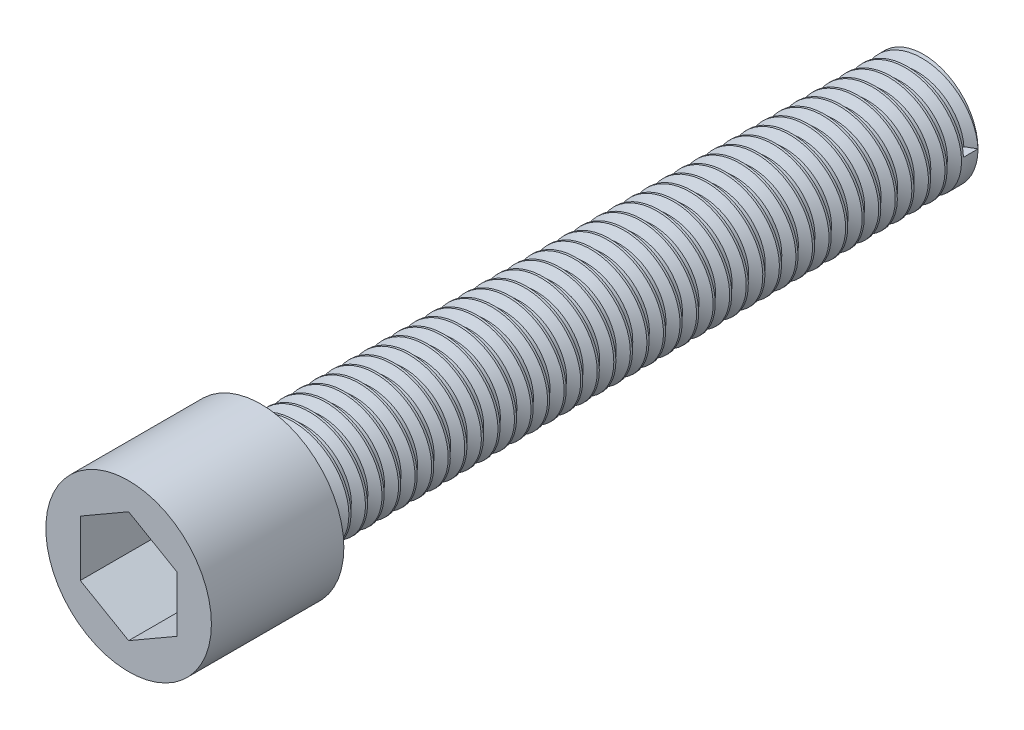
SolidWorks part; units mm, degrees
material "Aço carbono simples"
ref_plane "Plano frontal" through (0, 0, 0) normal (0, 0, 1) x (1, 0, 0)
ref_plane "Plano superior" through (0, 0, 0) normal (0, 1, 0) x (1, 0, 0)
ref_plane "Plano direito" through (0, 0, 0) normal (1, 0, 0) x (0, 0, -1)
sketch "Esboço1" plane through (0, 0, 0) normal (0, 0, 1) x (1, 0, 0)
  circle A0 centre (0, 0) radius 3.3
  dimension "D1" = 6.6
extrude "Ressalto-extrusão1" add sketch "Esboço1" along normal blind 40
sketch "Esboço2" plane through (0, 0, 40) normal (0, 0, 1) x (1, 0, 0)
  circle A0 centre (0, 0) radius 5
  dimension "D1" = 10
extrude "Ressalto-extrusão2" add sketch "Esboço2" along normal blind 8
sketch "Esboço3" plane through (0, 0, 48) normal (0, 0, 1) x (1, 0, 0)
  line L1 (0, 3.3704) -> (-2.9188, 1.6852)
  line L2 (-2.9188, 1.6852) -> (-2.9188, -1.6852)
  line L3 (-2.9188, -1.6852) -> (0, -3.3704)
  line L4 (0, -3.3704) -> (2.9188, -1.6852)
  line L5 (2.9188, -1.6852) -> (2.9188, 1.6852)
  line L6 (2.9188, 1.6852) -> (0, 3.3704)
  circle A0 centre (0, 0) radius 2.9188 construction
extrude "Corte-extrusão1" cut sketch "Esboço3" against normal blind 5
thread "Rosca1" pitch 1 method cut profile "Perfil da rosca2" start angle 0, offset 0, length 0, pitch 1, diameter 6.6
ref_plane "Plano2" through (3.3, 0, 0) normal (0, -1, 0) x (1, 0, 0)
sketch "Perfil da rosca2" plane through (3.3, 0, 0) normal (0, -1, 0) x (1, 0, 0)
  line L0 (0, 0) -> (0, 1) construction
  line L11 (0, 0) -> (0, 0.875)
  line L12 (0, 0.875) -> (-0.5413, 0.5625)
  line L13 (-0.5413, 0.5625) -> (-0.5413, 0.3125)
  line L15 (-0.5413, 0.3125) -> (0, 0)
  line L17 (-0.5413, 0.4375) -> (0, 0.4375) construction
  point P2 (0, 0)
  dimension "Pitch" = 1
  dimension "Profile_Angle" = 60
  dimension "Profile_Land" = 0.25
  dimension "Profile_Height" = 0.5413
